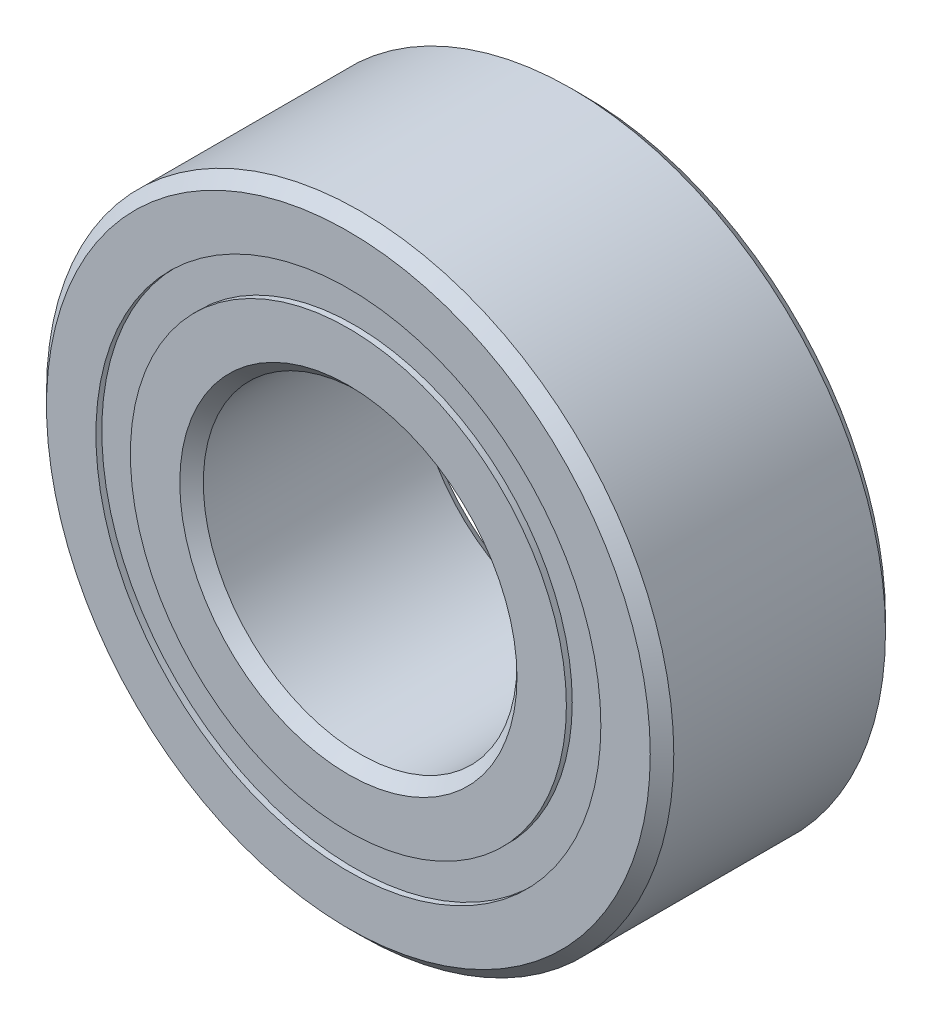
SolidWorks part; units mm, degrees
material "AISI 304"
ref_plane "Front Plane" through (0, 0, 0) normal (0, 0, 1) x (1, 0, 0)
ref_plane "Top Plane" through (0, 0, 0) normal (0, 1, 0) x (1, 0, 0)
ref_plane "Right Plane" through (0, 0, 0) normal (1, 0, 0) x (0, 0, -1)
sketch "Sketch1" plane through (0, 0, 0) normal (1, 0, 0) x (0, 0, -1)
  line L0 (-2.3813, 0) -> (2.3813, 0) construction
  line L1 (0, 6.35) -> (0, -6.35) construction
  line L2 (2.1431, 6.35) -> (-2.1431, 6.35)
  line L3 (-2.1431, 6.35) -> (-2.3813, 6.1119)
  line L4 (-2.3813, 6.1119) -> (-2.3813, 5.1114)
  line L5 (-2.3813, 5.1114) -> (-1.0583, 5.1114)
  line L6 (2.3813, 5.1114) -> (1.0583, 5.1114)
  line L7 (2.3813, 6.1119) -> (2.3813, 5.1114)
  line L8 (2.1431, 6.35) -> (2.3813, 6.1119)
  line L9 (0, 6.35) -> (0, 4.7625) construction
  line L10 (0, 4.7625) -> (0, 3.175) construction
  arc A0 (-1.0583, 5.1114) -> (1.0583, 5.1114) centre (0, 4.7625) cw
  point P14 (0, 3.175)
  dimension "D3" = 2.1167
  dimension "D1" = 45
  dimension "Width" = 4.7625
  dimension "OD" = 12.7
  dimension "D2" = 0.2381
  dimension "Shaft Dia" = 6.35
  dimension "D4" = 0.3489
revolve "Revolve1" add sketch "Sketch1" angle 360 about L0
sketch "Sketch3" plane through (0, 0, 0) normal (1, 0, 0) x (0, 0, -1)
  line L0 (-2.3813, 4.4136) -> (-1.0583, 4.4136)
  line L1 (0, 6.35) -> (0, -6.35) construction
  line L2 (-2.3813, 6.1119) -> (-2.3813, 5.1114) construction
  line L3 (-2.3813, 4.4136) -> (-2.3813, 3.4131)
  line L4 (-2.1431, 6.35) -> (-2.3813, 6.1119) construction
  line L5 (-2.3813, 3.4131) -> (-2.1431, 3.175)
  line L6 (-2.1431, 3.175) -> (2.1431, 3.175)
  line L7 (2.1431, 6.35) -> (2.1431, -6.35) construction
  line L8 (2.1431, 3.175) -> (2.3813, 3.4131)
  line L9 (2.3813, -6.1119) -> (2.3813, 6.1119) construction
  line L10 (2.3813, 3.4131) -> (2.3813, 4.4136)
  line L11 (2.3813, 4.4136) -> (1.0583, 4.4136)
  line L13 (2.1431, 6.35) -> (2.3813, 6.1119) construction
  arc A0 (1.0583, 5.1114) -> (-1.0583, 5.1114) centre (0, 4.7625) ccw construction
  arc A1 (1.0583, 4.4136) -> (-1.0583, 4.4136) centre (0, 4.7625) cw
revolve "Revolve3" add sketch "Sketch3" angle 360 about L0
sketch "Sketch4" plane through (0, 0, 0) normal (1, 0, 0) x (0, 0, -1)
  line L0 (-1.1144, 4.7625) -> (1.1144, 4.7625)
  arc A2 (-1.1144, 4.7625) -> (1.1144, 4.7625) centre (0, 4.7625) cw
  arc A3 (1.0583, 5.1114) -> (-1.0583, 5.1114) centre (0, 4.7625) ccw construction
revolve "Revolve4" add sketch "Sketch4" angle 360 about L0
ref_axis "Axis1" through (0, 0, -2.3813) along (0, 0, 1)
pattern_circular "CirPattern1" count 12 every 30 about axis through (0, 0, -2.3813) along (0, 0, 1) of bodies 104
sketch "Sketch6" plane through (0, 0, 0) normal (1, 0, 0) x (0, 0, -1)
  line L0 (-2.3813, 5.1114) -> (-1.0583, 5.1114) construction
  line L1 (-2.2622, 5.1114) -> (-1.1144, 5.1114)
  line L2 (-2.2622, 5.1114) -> (-2.2622, 4.4136)
  line L3 (-2.2622, 4.4136) -> (-1.1144, 4.4136)
  line L4 (-1.1144, 5.1114) -> (-1.1144, 4.4136)
  line L5 (-2.3813, 4.4136) -> (-1.0583, 4.4136) construction
  line L6 (2.3813, 5.1114) -> (1.0583, 5.1114) construction
  line L7 (2.2622, 5.1114) -> (1.1144, 5.1114)
  line L8 (2.2622, 5.1114) -> (2.2622, 4.4136)
  line L9 (2.2622, 4.4136) -> (1.1144, 4.4136)
  line L10 (1.1144, 5.1114) -> (1.1144, 4.4136)
  line L11 (2.3813, 4.4136) -> (1.0583, 4.4136) construction
  line L12 (-2.1431, 6.35) -> (-2.3813, 6.1119) construction
  point P18 (-2.2622, 6.2309)
revolve "Revolve5" add sketch "Sketch6" angle 360 about L0
equation "\"D2@Sketch1\" = \"Width@Sketch1\"*.05"
equation "\"D3@Sketch1\" = \"Width@Sketch1\"/2.25"
equation "\"D4@Sketch1\" = (((\"OD@Sketch1\"-\"Width@Sketch1\")/2)/3.25)/3.5"
equation "\"D2@CirPattern1\" = 360/\"Balls@CirPattern1\""
